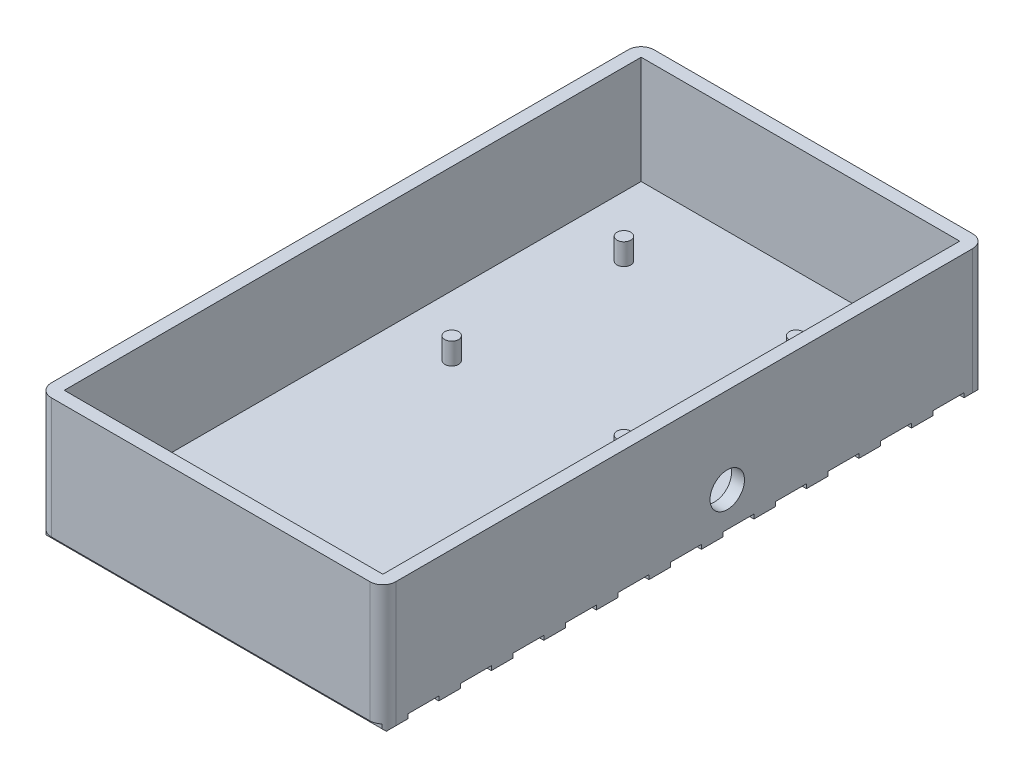
SolidWorks part; units mm, degrees
ref_plane "Front" through (0, 0, 0) normal (0, 0, 1) x (1, 0, 0)
ref_plane "Top" through (0, 0, 0) normal (0, 1, 0) x (1, 0, 0)
ref_plane "Right" through (0, 0, 0) normal (1, 0, 0) x (0, 0, -1)
sketch "Sketch1" plane through (0, 0, 0) normal (0, 1, 0) x (1, 0, 0)
  line L1 (-40, 70) -> (40, 70)
  line L2 (-40, 70) -> (-40, -70)
  line L3 (-40, -70) -> (40, -70)
  line L4 (40, 70) -> (40, -70)
  line L5 (-40, 70) -> (40, -70) construction
  line L6 (-40, -70) -> (40, 70) construction
  point P0 (0, 0)
  dimension "D1" = 80
  dimension "D2" = 140
extrude "Boss-Extrude1" add sketch "Sketch1" along normal blind 3
sketch "Sketch2" plane through (0, 3, 0) normal (0, 1, 0) x (1, 0, 0)
  line L0 (37, 67) -> (-37, 67)
  line L1 (-37, 67) -> (-37, -67)
  line L2 (-37, -67) -> (37, -67)
  line L3 (37, -67) -> (37, 67)
  line L4 (40, -70) -> (40, 70)
  line L5 (40, 70) -> (-40, 70)
  line L6 (-40, 70) -> (-40, -70)
  line L7 (-40, -70) -> (40, -70)
  line L8 (40, -70) -> (40, 70)
  line L9 (40, 70) -> (-40, 70)
  line L10 (-40, 70) -> (-40, -70)
  line L11 (-40, -70) -> (40, -70)
  dimension "D1" = 0
  dimension "D2" = 3
extrude "Boss-Extrude2" add sketch "Sketch2" along normal blind 25
sketch "Sketch3" plane through (0, 3, 0) normal (0, 1, 0) x (1, 0, 0)
  line L0 (-37, 49) -> (37, 49) construction
  line L1 (-37, 67) -> (-37, -67) construction
  line L2 (37, -67) -> (37, 67) construction
  line L3 (-37, 9) -> (37, 9) construction
  line L4 (37, -67) -> (37, 67) construction
  line L5 (37, 67) -> (-37, 67) construction
  line L6 (-3, 67) -> (-3, 9) construction
  circle A0 centre (-23, 49) radius 1.6
  circle A1 centre (-23, 9) radius 1.6
  circle A2 centre (17, 9) radius 1.6
  circle A3 centre (17, 49) radius 1.6
  dimension "D3" = 3.2
  dimension "D4" = 3.2
  dimension "D1" = 40
  dimension "D2" = 18
  dimension "D5" = 40
  dimension "D6" = 40
  dimension "D7" = 40
extrude "Boss-Extrude3" add sketch "Sketch3" along normal blind 5
sketch "Sketch4" plane through (0, 0, 0) normal (0, -1, 0) x (1, 0, 0)
  line L0 (40, 70) -> (40, -70) construction
  line L1 (-40, -70) -> (40, -70)
  line L2 (-40, -70) -> (-40, -65)
  line L3 (-40, -65) -> (40, -65)
  line L4 (40, -70) -> (40, -65)
  line L5 (-40, -57.8) -> (40, -57.8)
  line L6 (-40, -57.8) -> (-40, -52.8)
  line L7 (-40, -52.8) -> (40, -52.8)
  line L8 (40, -57.8) -> (40, -52.8)
  line L9 (-40, -45.6) -> (40, -45.6)
  line L10 (-40, -45.6) -> (-40, -40.6)
  line L11 (-40, -40.6) -> (40, -40.6)
  line L12 (40, -45.6) -> (40, -40.6)
  line L13 (-40, -33.4) -> (40, -33.4)
  line L14 (-40, -33.4) -> (-40, -28.4)
  line L15 (-40, -28.4) -> (40, -28.4)
  line L16 (40, -33.4) -> (40, -28.4)
  line L17 (-40, -21.2) -> (40, -21.2)
  line L18 (-40, -21.2) -> (-40, -16.2)
  line L19 (-40, -16.2) -> (40, -16.2)
  line L20 (40, -21.2) -> (40, -16.2)
  line L21 (-40, -9) -> (40, -9)
  line L22 (-40, -9) -> (-40, -4)
  line L23 (-40, -4) -> (40, -4)
  line L24 (40, -9) -> (40, -4)
  line L25 (-40, 3.2) -> (40, 3.2)
  line L26 (-40, 3.2) -> (-40, 8.2)
  line L27 (-40, 8.2) -> (40, 8.2)
  line L28 (40, 3.2) -> (40, 8.2)
  line L29 (-40, 15.4) -> (40, 15.4)
  line L30 (-40, 15.4) -> (-40, 20.4)
  line L31 (-40, 20.4) -> (40, 20.4)
  line L32 (40, 15.4) -> (40, 20.4)
  line L33 (-40, 27.6) -> (40, 27.6)
  line L34 (-40, 27.6) -> (-40, 32.6)
  line L35 (-40, 32.6) -> (40, 32.6)
  line L36 (40, 27.6) -> (40, 32.6)
  line L37 (-40, 39.8) -> (40, 39.8)
  line L38 (-40, 39.8) -> (-40, 44.8)
  line L39 (-40, 44.8) -> (40, 44.8)
  line L40 (40, 39.8) -> (40, 44.8)
  line L41 (-40, 52) -> (40, 52)
  line L42 (-40, 52) -> (-40, 57)
  line L43 (-40, 57) -> (40, 57)
  line L44 (40, 52) -> (40, 57)
  line L45 (-40, 64.2) -> (40, 64.2)
  line L46 (-40, 64.2) -> (-40, 69.2)
  line L47 (-40, 69.2) -> (40, 69.2)
  line L48 (40, 64.2) -> (40, 69.2)
  dimension "D1" = 5
  dimension "D2" = 12
extrude "Boss-Extrude4" add sketch "Sketch4" along normal blind 2
chamfer "Chamfer1" distance 1 angle 45 48 edges at (0, -2, 69.2) (40, -2, 66.7) (0, -2, 64.2) (-40, -2, 66.7) (0, -2, 57) (40, -2, 54.5) (0, -2, 52) (-40, -2, 54.5) (0, -2, 44.8) (40, -2, 42.3) (0, -2, 39.8) (-40, -2, 42.3) (0, -2, 32.6) (40, -2, 30.1) (0, -2, 27.6) (-40, -2, 30.1) (0, -2, 20.4) (40, -2, 17.9) (0, -2, 15.4) (-40, -2, 17.9) (0, -2, 8.2) (40, -2, 5.7) (0, -2, 3.2) (-40, -2, 5.7) (0, -2, -4) (40, -2, -6.5) (0, -2, -9) (-40, -2, -6.5) (0, -2, -16.2) (40, -2, -18.7) (0, -2, -21.2) (-40, -2, -18.7) (0, -2, -28.4) (40, -2, -30.9) (0, -2, -33.4) (-40, -2, -30.9) (0, -2, -40.6) (40, -2, -43.1) (0, -2, -45.6) (-40, -2, -43.1) (0, -2, -52.8) (40, -2, -55.3) (0, -2, -57.8) (-40, -2, -55.3) (0, -2, -65) (40, -2, -67.5) (0, -2, -70) (-40, -2, -67.5)
sketch "Sketch5" plane through (40, 0, 0) normal (1, 0, 0) x (0, 0, -1)
  line L0 (10, 28) -> (10, 0) construction
  line L1 (-70, 28) -> (70, 28) construction
  line L2 (9, 0) -> (16.2, 0) construction
  line L3 (70, 28) -> (70, -1) construction
  circle A0 centre (10, 8) radius 4
  dimension "D1" = 8
  dimension "D2" = 8
  dimension "D3" = 60
extrude "Cut-Extrude1" cut sketch "Sketch5" against normal blind 10
fillet "Fillet1" radius 3 4 edges at (40, 14, 70) (-40, 14, 70) (40, 13.5, -70) (-40, 13.5, -70)
